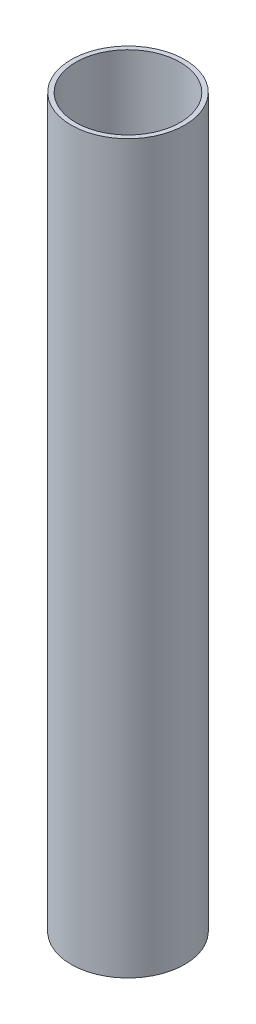
SolidWorks part; units mm, degrees
material "ПВХ 0.007 Смягченный"
ref_plane "Спереди" through (0, 0, 0) normal (0, 0, 1) x (1, 0, 0)
ref_plane "Сверху" through (0, 0, 0) normal (0, 1, 0) x (1, 0, 0)
ref_plane "Справа" through (0, 0, 0) normal (1, 0, 0) x (0, 0, -1)
sketch "Эскиз1" plane through (0, 0, 0) normal (0, 1, 0) x (1, 0, 0)
  circle A0 centre (0, 0) radius 25
  circle A1 centre (0, 0) radius 23
  dimension "ExDBody" = 50
  dimension "InDBody" = 46
extrude "Бобышка-Вытянуть1" add sketch "Эскиз1" along normal blind 320
